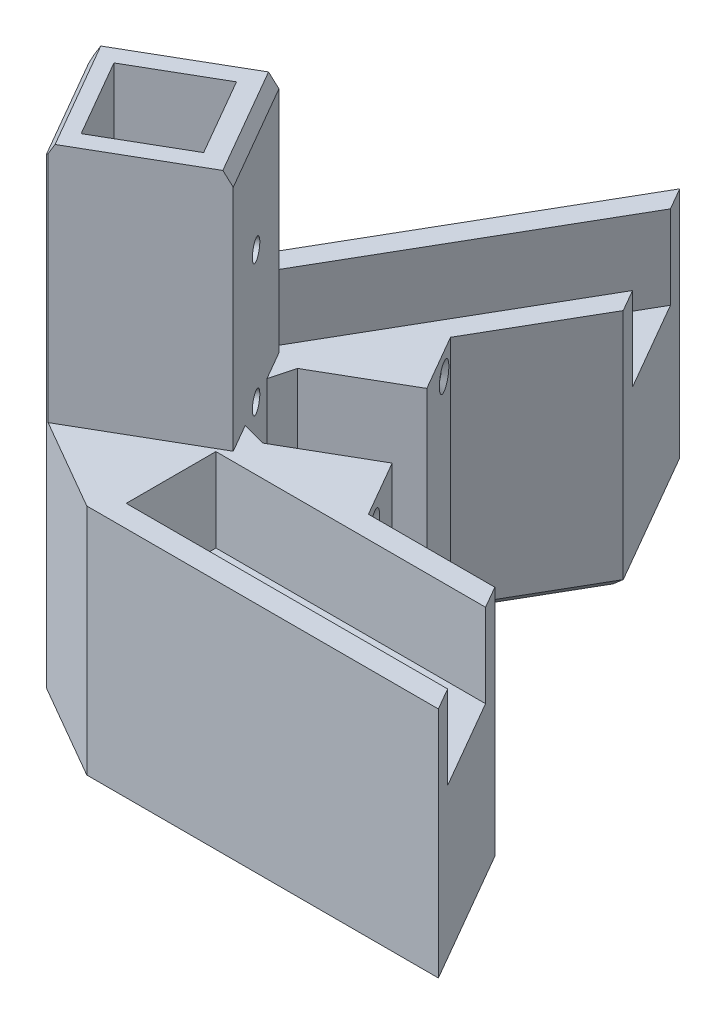
SolidWorks part; units mm, degrees
other "Markup1"
sketch "Sketch26" plane through (25.6218, 0, -129.9038) normal (-0.1134, -0.9932, -0.0259) x (0.9576, -0.1162, 0.2636)
ref_plane "Front Plane" through (0, 0, 0) normal (0, 0, 1) x (1, 0, 0)
ref_plane "Top Plane" through (0, 0, 0) normal (0, 1, 0) x (1, 0, 0)
ref_plane "Right Plane" through (0, 0, 0) normal (1, 0, 0) x (0, 0, -1)
sketch "Sketch1" plane through (0, 0, 0) normal (0, 1, 0) x (1, 0, 0)
  line L0 (0, 0) -> (150, 0)
  line L1 (0, 0) -> (75, 129.9038)
  line L2 (75, 129.9038) -> (150, 0)
  dimension "D1" = 60
  dimension "D2" = 150
  dimension "D3" = 60
sketch "Sketch2" plane through (0, 0, 0) normal (0, 1, 0) x (1, 0, 0)
  line L1 (74.2, 5.2) -> (174.2, 5.2) construction
  line L2 (74.2, 5.2) -> (74.2, 25.2) construction
  line L3 (74.2, 25.2) -> (174.2, 25.2) construction
  line L4 (174.2, 5.2) -> (174.2, 25.2) construction
  line L5 (41.6033, 61.6591) -> (91.6033, 148.2616) construction
  line L6 (91.6033, 148.2616) -> (108.9238, 138.2616) construction
  line L7 (108.9238, 138.2616) -> (58.9238, 51.6591) construction
  line L8 (58.9238, 51.6591) -> (41.6033, 61.6591) construction
  line L9 (0, 0) -> (150, 0) construction
  line L10 (109.197, 138.3348) -> (58.997, 51.3859)
  line L11 (58.997, 51.3859) -> (41.3301, 61.5859)
  line L12 (41.3301, 61.5859) -> (91.5301, 148.5348)
  line L13 (91.5301, 148.5348) -> (109.197, 138.3348)
  line L14 (74, 25.4) -> (174.4, 25.4)
  line L15 (174.4, 5) -> (174.4, 25.4)
  line L16 (74, 5) -> (174.4, 5)
  line L17 (74, 5) -> (74, 25.4)
  line L18 (0, 0) -> (75, 129.9038) construction
  dimension "D1" = 20
  dimension "D2" = 5
  dimension "D3" = 74
  dimension "D4" = 20
  dimension "D5" = 74
  dimension "D6" = 5
  dimension "D7" = 100
  dimension "D8" = 100
  dimension "D9" = 0.2
  dimension "D10" = 0.2
sketch "Sketch4" plane through (0, 0, 0) normal (0, 1, 0) x (1, 0, 0)
  line L4 (0, 0) -> (54.7796, 31.6328) construction
  line L6 (0, 0) -> (53.0061, 91.8093) construction
  line L7 (68.4402, 27.9736) -> (51.1204, 17.9723) construction
  line L8 (68.4402, 27.9736) -> (58.4388, 45.2934) construction
  line L9 (58.4388, 45.2934) -> (41.1191, 35.292) construction
  line L10 (51.1204, 17.9723) -> (41.1191, 35.292) construction
  line L11 (68.4402, 27.9736) -> (41.1191, 35.292) construction
  line L12 (58.4388, 45.2934) -> (51.1204, 17.9723) construction
  line L13 (58.512, 45.5666) -> (40.8459, 35.3652)
  line L15 (0, 0) -> (131.24, 0) construction
  line L17 (51.0473, 17.6991) -> (40.8459, 35.3652)
  line L18 (68.7134, 27.9005) -> (51.0473, 17.6991)
  line L19 (68.7134, 27.9005) -> (58.512, 45.5666)
  point P0 (54.7796, 31.6328)
  dimension "D1" = 20
  dimension "D2" = 20
  dimension "D3" = 30.005
  dimension "D4" = 0.2
  dimension "D5" = 63.2569
  dimension "D6" = 60
ref_plane "Plane1" through (4.3301, 0, 2.5) normal (0.866, 0, 0.5) x (0.5, 0, -0.866)
ref_plane "Plane2" through (21.997, 0, 12.7) normal (-0.866, 0, -0.5) x (-0.5, 0, 0.866)
ref_plane "Plane3" through (0, 0, -25.4) normal (0, 0, 1) x (1, 0, 0)
ref_plane "Plane4" through (0, 0, -5) normal (0, 0, 1) x (1, 0, 0)
ref_plane "Plane6" through (-5.1007, 0, -8.8331) normal (-0.5001, 0, -0.866) x (-0.866, 0, 0.5001)
ref_plane "Plane7" through (5.1007, 0, 8.8331) normal (-0.5001, 0, -0.866) x (-0.866, 0, 0.5001)
extrude "Boss-Extrude1" add sketch "Sketch1" against normal blind 55
extrude "Cut-Extrude2" cut sketch "Sketch4" against normal through all and the other way through all
extrude "Cut-Extrude3" cut sketch "Sketch2" against normal blind 19
sketch "Sketch27" plane through (0, 0, 0) normal (0, 1, 0) x (1, 0, 0)
  line L0 (92.5514, 99.5038) -> (63.4254, 49.0561)
  line L1 (135.3353, 25.4) -> (89.6647, 104.5038) construction
  line L2 (63.4254, 49.0561) -> (74.1985, 30.4)
  line L3 (74.1985, 30.4) -> (132.4486, 30.4)
  line L4 (58.997, 51.3859) -> (89.6647, 104.5038) construction
  line L5 (135.3353, 25.4) -> (74, 25.4) construction
  line L6 (58.512, 45.5666) -> (68.7134, 27.9005) construction
  line L7 (58.997, 51.3859) -> (89.6647, 104.5038) construction
  line L8 (74, 25.4) -> (135.3353, 25.4) construction
  dimension "D1" = 5
  dimension "D2" = 5
  dimension "D3" = 6
extrude "Cut-Extrude4" cut sketch "Sketch27" against normal through all and the other way through all
sketch "Sketch28" plane through (0, 0, 0) normal (0, 1, 0) x (1, 0, 0)
  line L1 (92.5514, 99.5038) -> (63.4254, 49.0561) construction
  line L2 (74.1985, 30.4) -> (132.4486, 30.4) construction
  line L3 (63.4254, 49.0561) -> (74.1985, 30.4) construction
  line L5 (63.4254, 49.0561) -> (78.1721, 74.598)
  line L6 (78.1721, 74.598) -> (85.5454, 61.8294)
  line L7 (103.6944, 30.4) -> (74.1985, 30.4)
  line L8 (85.5454, 61.8294) -> (63.4254, 49.0561)
  line L9 (74.1985, 30.4) -> (96.3184, 43.1733)
  line L10 (96.3184, 43.1733) -> (103.6944, 30.4)
  dimension "D1" = 105
sketch "Sketch36" plane through (0, 0, 0) normal (0, 1, 0) x (1, 0, 0)
  line L0 (0, 0) -> (27.7444, 48.0548)
  line L1 (75, 129.9038) -> (0, 0) construction
  line L2 (27.7444, 48.0548) -> (55.4939, 0)
  line L3 (0, 0) -> (150, 0) construction
  line L4 (55.4939, 0) -> (0, 0)
  line L5 (51.0473, 17.6991) -> (40.8459, 35.3652) construction
  dimension "D1" = 5
extrude "Cut-Extrude12" cut sketch "Sketch36" against normal through all
sketch "Sketch37" plane through (0, 0, 0) normal (0, 1, 0) x (1, 0, 0)
  line L0 (34.5157, 36.3288) -> (61.7076, 52.0309)
  line L3 (55.4939, 0) -> (27.7444, 48.0548) construction
  line L6 (40.8459, 35.3652) -> (58.512, 45.5666) construction
  line L7 (48.7176, 11.7348) -> (75.9096, 27.4369)
  line L9 (68.7134, 27.9005) -> (51.0473, 17.6991) construction
  line L10 (61.7076, 52.0309) -> (75.9096, 27.4369)
  line L14 (58.512, 45.5666) -> (68.7134, 27.9005) construction
  line L15 (34.5157, 36.3288) -> (48.7176, 11.7348)
  line L16 (58.512, 45.5666) -> (40.8459, 35.3652)
  line L17 (40.8459, 35.3652) -> (51.0473, 17.6991)
  line L18 (51.0473, 17.6991) -> (68.7134, 27.9005)
  line L19 (68.7134, 27.9005) -> (58.512, 45.5666)
  dimension "D1" = 4
  dimension "D2" = 4
  dimension "D3" = 6
extrude "Boss-Extrude2" add sketch "Sketch37" along normal blind 55
chamfer "Chamfer1" distance 14.54 angle 30 1 edges at (27.7444, -27.5, -48.0548) first distance on face at (41.6179, 0, -24.0296)
chamfer "Chamfer8" distance 14.54 angle 30 1 edges at (55.4939, -27.5, 0) first distance on face at (102.747, -27.5, 0)
chamfer "Chamfer10" distance 3 angle 30 2 edges at (41.6187, 55, -24.0282) (68.8086, 55, -39.7339) first distance on face at (41.6187, 0, -24.0282) first distance on face at (68.8103, 0, -39.731)
extrude "Boss-Extrude4" add sketch "Sketch28" against normal up to surface (55 mm away) up to face at (77.5909, -55, -44.7965)
sketch "Sketch39" plane through (90.9285, 0, -52.5072) normal (0.866, 0, -0.5001) x (-0.5001, 0, -0.866)
  line L0 (-25.5284, 0) -> (-10.7784, 0) construction
  line L1 (-21.5, -48) -> (21.5, -48) construction
  line L2 (-21.5, -48) -> (-21.5, -5) construction
  line L3 (-21.5, -5) -> (21.5, -5) construction
  line L4 (21.5, -48) -> (21.5, -5) construction
  line L5 (-21.5, -48) -> (21.5, -5) construction
  line L6 (-21.5, -5) -> (21.5, -48) construction
  circle A0 centre (-21.5, -5) radius 1.95
  circle A1 centre (21.5, -5) radius 1.95
  circle A2 centre (21.5, -48) radius 1.95
  circle A3 centre (-21.5, -48) radius 1.95
  point P0 (0, -26.5)
  dimension "D4" = 3.9
  dimension "D1" = 43
  dimension "D2" = 43
  dimension "D3" = 5
extrude "Cut-Extrude13" cut sketch "Sketch39" against normal blind 11
sketch "Sketch40" plane through (0, -19, 0) normal (0, 1, 0) x (1, 0, 0)
  line L0 (50.1636, 56.4859) -> (83.7757, 114.7038) construction
  line L1 (41.3301, 61.5859) -> (58.997, 51.3859) construction
  line L2 (89.6647, 104.5038) -> (77.8868, 124.9038) construction
  circle A0 centre (76.2757, 101.7134) radius 2.3
  circle A1 centre (57.6636, 69.4763) radius 2.3
  dimension "D1" = 4.6
  dimension "D2" = 15
  dimension "D3" = 15
extrude "Cut-Extrude14" cut sketch "Sketch40" against normal through all
sketch "Sketch41" plane through (0, -19, 0) normal (0, 1, 0) x (1, 0, 0)
  line L0 (74, 15.2) -> (141.2243, 15.2) construction
  line L1 (74, 25.4) -> (74, 5) construction
  line L2 (147.1132, 5) -> (135.3353, 25.4) construction
  circle A0 centre (89, 15.2) radius 2.3
  circle A1 centre (126.2243, 15.2) radius 2.3
  dimension "D1" = 4.6
  dimension "D2" = 15
  dimension "D3" = 15
extrude "Cut-Extrude15" cut sketch "Sketch41" against normal through all
ref_plane "Plane8" through (0, -24, 0) normal (0, 1, 0) x (1, 0, 0)
sketch "Sketch42" plane through (0, -24, 0) normal (0, 1, 0) x (1, 0, 0)
  circle A0 centre (76.2757, 101.7134) radius 5
  circle A1 centre (57.6636, 69.4763) radius 5
  circle A2 centre (89, 15.2) radius 5
  circle A3 centre (126.2243, 15.2) radius 5
  dimension "D1" = 10
extrude "Cut-Extrude16" cut sketch "Sketch42" against normal through all
chamfer "Chamfer6" distance 1 angle 45 4 edges at (49.6789, -55, -40.4659) (45.9466, -55, -26.5321) (59.8803, -55, -22.7998) (63.6127, -55, -36.7335)
chamfer "Chamfer13" distance 2 angle 45 4 edges at (126.2243, -55, -10.2) (89, -55, -10.2) (76.2757, -55, -96.7134) (57.6636, -55, -64.4763)
chamfer "Chamfer14" distance 4 angle 45 2 edges at (63.4254, -27.5, -49.0561) (74.1985, -27.5, -30.4)
sketch "Sketch35" plane through (45.9466, 0, -26.5321) normal (0.866, 0, -0.5001) x (-0.5001, 0, -0.866)
  line L0 (0, 0) -> (0, -55) construction
  circle A0 centre (0, -30) radius 2.3
  circle A1 centre (0, 0) radius 2.3
  circle A2 centre (0, 30) radius 2.3
  dimension "D3" = 4.6
  dimension "D1" = 30
  dimension "D4" = 30
extrude "Cut-Extrude11" cut sketch "Sketch35" along normal through all
chamfer "Chamfer15" distance 1 angle 45 4 edges at (79.2019, -48, -72.8146) (100.7048, -48, -35.5772) (100.7048, -5, -35.5772) (79.2019, -5, -72.8146)
chamfer "Chamfer12" distance 2 angle 45 16 edges at (86.9905, -55, -37.7868) (100.0064, -55, -36.7866) (118.0715, -55, -30.4) (141.2243, -55, -15.2) (110.017, -55, 0) (59.1279, -55, -6.2966) (41.6187, -55, -24.0282) (35.0144, -55, -48.0542) (55.0067, -55, -95.2744) (83.7757, -55, -114.7038) (85.3618, -55, -87.0509) (81.8587, -55, -68.2137) (76.2174, -55, -56.4429) (68.812, -55, -39.728) (66.1576, -55, -48.3243) (74.9304, -55, -33.1321)
